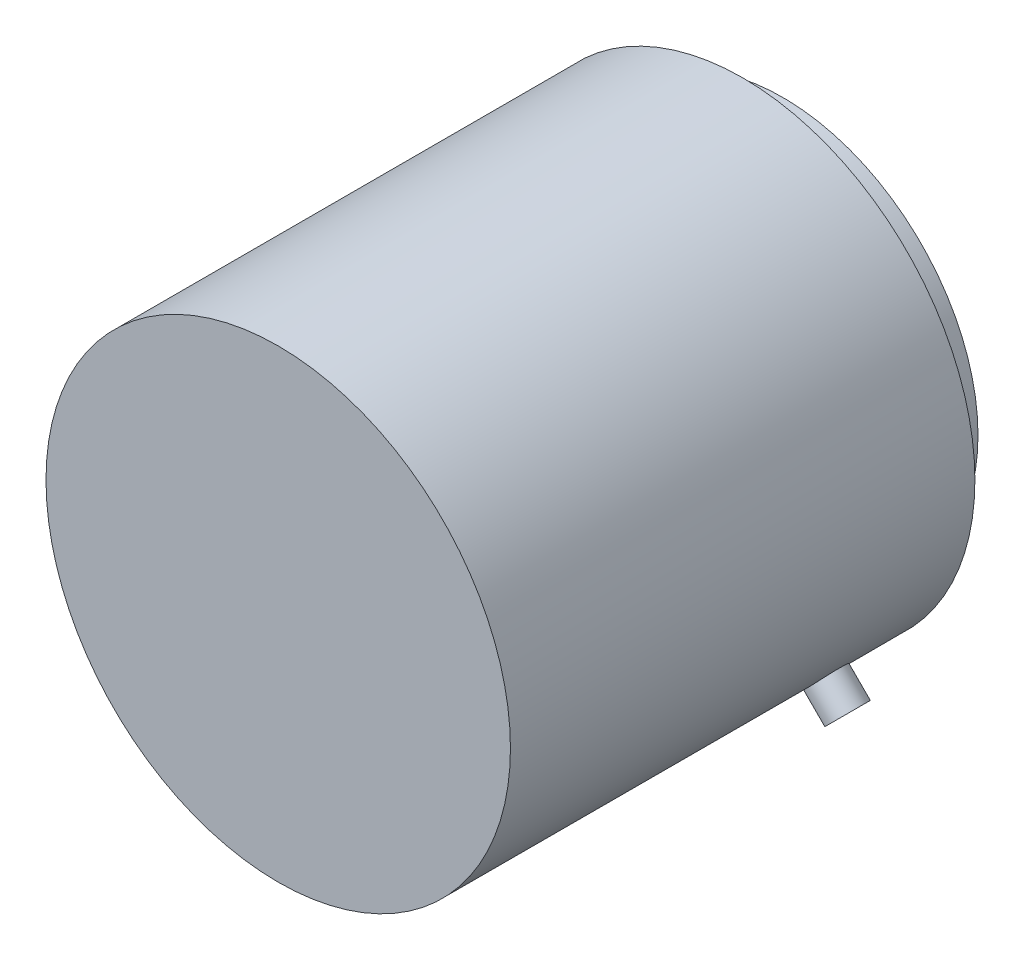
SolidWorks part; units mm, degrees
ref_plane "Front Plane" through (0, 0, 0) normal (0, 0, 1) x (1, 0, 0)
ref_plane "Top Plane" through (0, 0, 0) normal (0, 1, 0) x (1, 0, 0)
ref_plane "Right Plane" through (0, 0, 0) normal (1, 0, 0) x (0, 0, -1)
sketch "Sketch1" plane through (0, 0, 0) normal (0, 0, 1) x (1, 0, 0)
  circle A0 centre (0, 0) radius 37.5
  dimension "D1" = 75
extrude "Boss-Extrude1" add sketch "Sketch1" along normal blind 75
sketch "Sketch2" plane through (0, 0, 0) normal (0, 0, -1) x (-1, 0, 0)
  circle A0 centre (0, 0) radius 31.5
  dimension "D1" = 63
extrude "Boss-Extrude2" add sketch "Sketch2" along normal blind 6.5
sketch "Sketch3" plane through (0, 0, -6.5) normal (0, 0, -1) x (-1, 0, 0)
  circle A0 centre (0, 0) radius 15.75
  dimension "D1" = 31.5
extrude "Cut-Extrude1" cut sketch "Sketch3" against normal blind 6.5
sketch "Sketch4" plane through (0, 0, -6.5) normal (0, 0, -1) x (-1, 0, 0)
  circle A0 centre (25, 0) radius 3
  circle A1 centre (0, -25) radius 3
  circle A2 centre (-25, 0) radius 3
  circle A3 centre (0, 25) radius 3
  circle A4 centre (0, 0) radius 25
  dimension "D1" = 50
extrude "Cut-Extrude2" cut sketch "Sketch4" against normal blind 5 contours A0 A4 | A4 A3 | A3 A4 | A0 | A2 | A1 region at (-23.6949, 0, -6.5) region at (0, 26.2403, -6.5) region at (0, 23.6949, -6.5)
sketch "Sketch6" plane through (0, 0, 0) normal (0, 0, -1) x (-1, 0, 0)
  line L0 (0, 0) -> (-41.0527, -41.0527)
  line L1 (-22.1632, -26.4059) -> (-26.4059, -22.1632)
  line L2 (-22.1632, -26.4059) -> (-27.8201, -32.0627)
  line L3 (-27.8201, -32.0627) -> (-32.0627, -27.8201)
  line L4 (-32.0627, -27.8201) -> (-26.4059, -22.1632)
  circle M7 centre (0, 0) radius 37.5
  dimension "D1" = 6
  dimension "D2" = 3
  dimension "D3" = 8
extrude "Boss-Extrude3" add sketch "Sketch6" against normal blind 6 from offset 10 contours L3 L2 L0 M7 | L4 L3 L0 M7 region at (27.1497, -29.2797, 0) region at (29.2797, -27.1497, 0) offset against normal yes
sketch "Sketch7" plane through (29.9414, -29.9414, 0) normal (0.7071, -0.7071, 0) x (0, 0, -1)
  circle A0 centre (-13, 0) radius 3
  circle A1 centre (-13, 0) radius 7.956
extrude "Cut-Extrude4" cut sketch "Sketch7" against normal up to surface (4.9637 mm away) up to face at (37.5, 0, 0)
